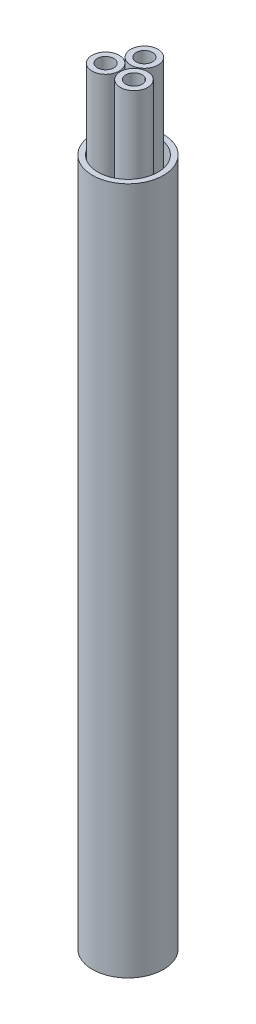
SolidWorks part; units mm, degrees
material "PTFE (general)"
ref_plane "Front Plane" through (0, 0, 0) normal (0, 0, 1) x (1, 0, 0)
ref_plane "Top Plane" through (0, 0, 0) normal (0, 1, 0) x (1, 0, 0)
ref_plane "Right Plane" through (0, 0, 0) normal (1, 0, 0) x (0, 0, -1)
sketch "Sketch1" plane through (0, 0, 0) normal (0, 1, 0) x (1, 0, 0)
  line L0 (-1.3, -0.7506) -> (0, 1.5011) construction
  line L1 (0, 1.5011) -> (1.3, -0.7506) construction
  line L2 (1.3, -0.7506) -> (-1.3, -0.7506) construction
  circle A0 centre (-1.3, -0.7506) radius 1.25
  circle A1 centre (0, 1.5011) radius 1.25
  circle A2 centre (1.3, -0.7506) radius 1.25
  circle A3 centre (0, 0) radius 2.7511
  circle A4 centre (0, 0) radius 3.2511
  circle A5 centre (-1.3, -0.7506) radius 0.75
  circle A6 centre (0, 1.5011) radius 0.75
  circle A7 centre (1.3, -0.7506) radius 0.75
  dimension "D1" = 1.5
  dimension "D2" = 0.5
  dimension "D3" = 2.6
  dimension "D4" = 0.5
extrude "Boss-Extrude1" add sketch "Sketch1" along normal blind 70 contours A0 A5 | A1 A6 | A2 A7 region at (-0.9856, 0, 1.9238) region at (0.1267, 0, 0.4362) region at (0.8589, 0, -2.36)
extrude "Boss-Extrude2" add sketch "Sketch1<3>" along normal blind 63 separate body contours A4 A3 region at (-3.1592, 0, 0)
sketch "Sketch1<3>" plane through (0, 0, 0) normal (0, 1, 0) x (1, 0, 0) same geometry as "Sketch1"
equation "\"d_cable\"= 1.5"
equation "\"t_iso_1\"= 0.5"
equation "\"t_iso_2\"= 0.5"
equation "\"L\"= 70"
equation "\"D1@Sketch1\"=\"d_cable\""
equation "\"D2@Sketch1\"=\"t_iso_1\""
equation "\"D3@Sketch1\"=0.1mm+(\"d_cable\"+2*\"t_iso_1\")"
equation "\"D4@Sketch1\"=\"t_iso_2\""
equation "\"D1@Boss-Extrude1\"=\"L\""
equation "\"D1@Boss-Extrude2\"=\"L\"*0.9"
